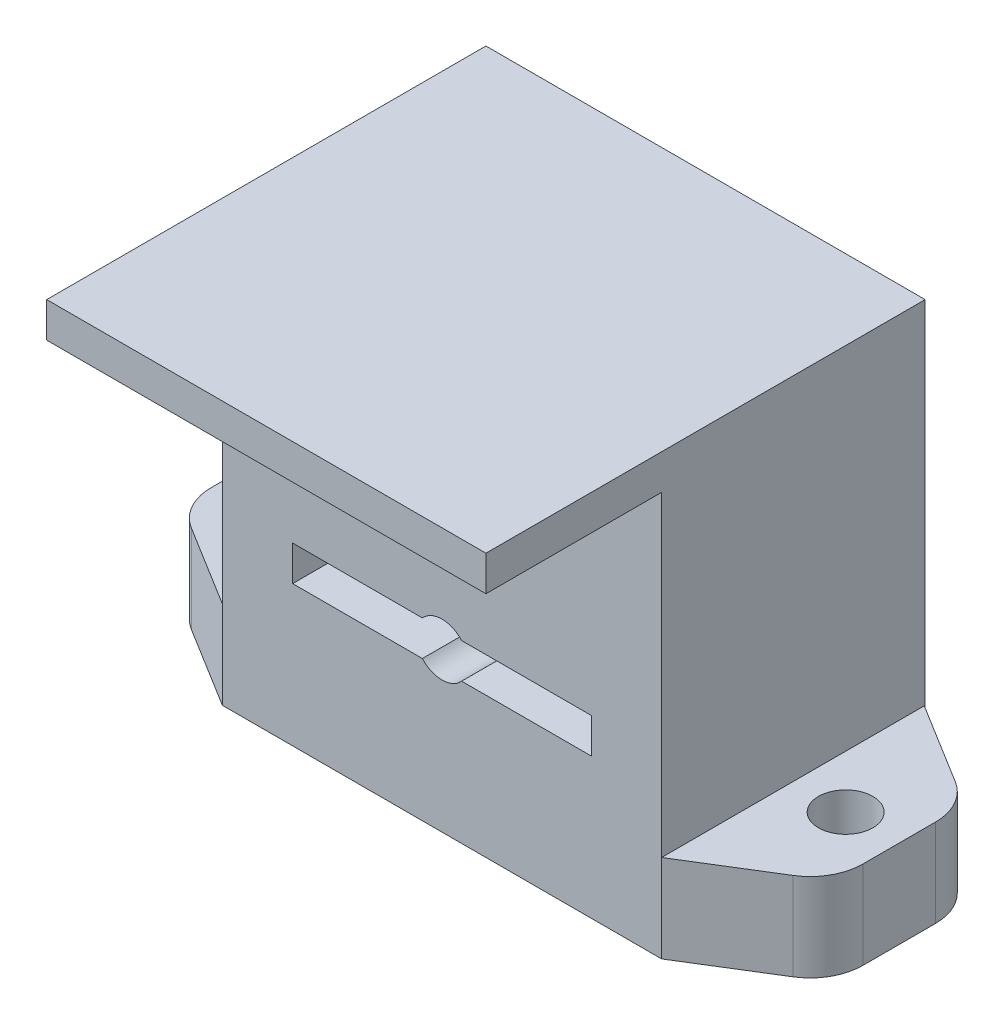
SolidWorks part; units mm, degrees
ref_plane "Front Plane" through (0, 0, 0) normal (0, 0, 1) x (1, 0, 0)
ref_plane "Top Plane" through (0, 0, 0) normal (0, 1, 0) x (1, 0, 0)
ref_plane "Right Plane" through (0, 0, 0) normal (1, 0, 0) x (0, 0, -1)
sketch "Sketch1" plane through (0, 0, 0) normal (0, 0, 1) x (1, 0, 0)
  line L0 (0, 12.5) -> (0, -12.5) construction
  line L1 (-12.5, 12.5) -> (12.5, 12.5)
  line L2 (-12.5, 12.5) -> (-12.5, -12.5)
  line L3 (-12.5, -12.5) -> (12.5, -12.5)
  line L4 (12.5, 12.5) -> (12.5, -12.5)
  line L5 (-12.5, 12.5) -> (12.5, -12.5) construction
  line L6 (-12.5, -12.5) -> (12.5, 12.5) construction
  line L12 (8.5, -4.5) -> (-8.5, -4.5)
  line L13 (8.5, -4.5) -> (8.5, -2.5)
  line L14 (8.5, -2.5) -> (-8.5, -2.5)
  line L15 (-8.5, -4.5) -> (-8.5, -2.5)
  line L16 (8.5, -4.5) -> (-8.5, -2.5) construction
  line L17 (8.5, -2.5) -> (-8.5, -4.5) construction
  line L18 (8.5, 7.5) -> (-8.5, 7.5)
  line L19 (8.5, 7.5) -> (8.5, 9.5)
  line L20 (8.5, 9.5) -> (-8.5, 9.5)
  line L21 (-8.5, 7.5) -> (-8.5, 9.5)
  line L22 (8.5, 7.5) -> (-8.5, 9.5) construction
  line L23 (8.5, 9.5) -> (-8.5, 7.5) construction
  line L24 (-12.5, 12.5) -> (12.5, 12.5)
  line L25 (-12.5, 12.5) -> (-12.5, 10.5)
  line L26 (-12.5, 10.5) -> (12.5, 10.5)
  line L27 (12.5, 12.5) -> (12.5, 10.5)
  circle A2 centre (0, 8.5) radius 1.5
  circle A3 centre (0, -3.5) radius 1.5
  point P0 (0, 0)
  point P10 (0, -3.5)
  point P15 (0, 8.5)
  dimension "D7" = 2
  dimension "D1" = 25
  dimension "D2" = 25
  dimension "D3" = 8
  dimension "D4" = 10
  dimension "D5" = 17
  dimension "D6" = 2
  dimension "D8" = 2
  dimension "D9" = 17
extrude "Boss-Extrude1" add sketch "Sketch1" along normal blind 15 contours L4 L1 L2 L3 L12 L15 L14 L13 L18 L21 L20 L19 region at (0, -1.4938, 0)
extrude "Boss-Extrude4" add sketch "Sketch1<5>" along normal blind 5 contours A2 L20 L21 L18 | A2 L18 L19 L20 | A3 L12 L13 L14 | A3 L14 L15 L12 region at (4.9391, -3.5, 0) region at (-4.9391, -3.5, 0) region at (4.9391, 8.5, 0) region at (-4.9391, 8.5, 0)
sketch "Sketch1<5>" plane through (0, 0, 0) normal (0, 0, 1) x (1, 0, 0) same geometry as "Sketch1"
sketch "Sketch3" plane through (0, -12.5, 0) normal (0, -1, 0) x (1, 0, 0)
  line L0 (0, 0) -> (0, 15) construction
  line L1 (18.5483, 5.4613) -> (18.5483, 9.59)
  line L6 (12.5, 0.0513) -> (17.1252, 2.9092)
  line L7 (17.1252, 12.1421) -> (12.5, 15)
  line L8 (-17.1252, 12.1421) -> (-12.5, 15)
  line L9 (-12.5, 0.0513) -> (-17.1252, 2.9092)
  line L10 (-18.5483, 5.4613) -> (-18.5483, 9.59)
  line L11 (-12.5, 15) -> (12.5, 15) construction
  circle A0 centre (-15.5, 7.5257) radius 1.55
  arc A1 (-18.5483, 9.59) -> (-17.1252, 12.1421) centre (-15.5483, 9.59) cw
  arc A2 (-18.5483, 5.4613) -> (-17.1252, 2.9092) centre (-15.5483, 5.4613) ccw
  arc A3 (18.5483, 5.4613) -> (17.1252, 2.9092) centre (15.5483, 5.4613) cw
  arc A4 (18.5483, 9.59) -> (17.1252, 12.1421) centre (15.5483, 9.59) ccw
  circle A5 centre (15.5, 7.5257) radius 1.55
  line M8 (12.5, 0) -> (12.5, 15)
  line M10 (-12.5, 15) -> (-12.5, 0)
  dimension "D1" = 3.1
extrude "Boss-Extrude5" add sketch "Sketch3" against normal blind 5 contours L10 A2 L9 L8 A1 A0 M10 | L1 A4 L7 L6 A3 A5 M8 region at (18.0276, -12.5, 4.0788) region at (-14.7278, -12.5, 13.4339)
extrude "Boss-Extrude6" add sketch "Sketch1<6>" along normal blind 25 contours L2 L26 L4 L1 region at (0, 11.5, 0)
sketch "Sketch1<6>" plane through (0, 0, 0) normal (0, 0, 1) x (1, 0, 0) same geometry as "Sketch1"
